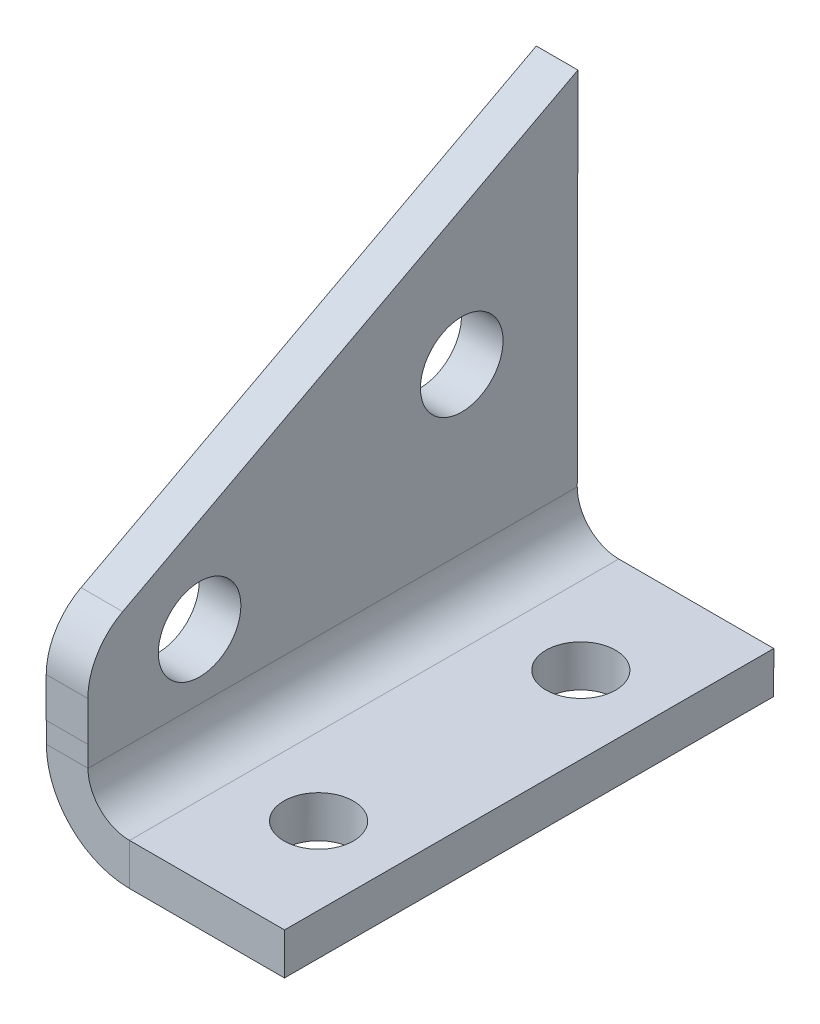
SolidWorks part; units mm, degrees
note: The reader was unsure of these and kept them because the rebuilt part matched: flange length of "Edge-Flange1".
ref_plane "Front Plane" through (0, 0, 0) normal (0, 0, 1) x (1, 0, 0)
ref_plane "Top Plane" through (0, 0, 0) normal (0, 1, 0) x (1, 0, 0)
ref_plane "Right Plane" through (0, 0, 0) normal (1, 0, 0) x (0, 0, -1)
sketch "Sketch2" plane through (0, 0, 0) normal (1, 0, 0) x (0, 0, -1)
  line L0 (83.1061, 32.1051) -> (83.1692, 65.9702)
  line L1 (83.1692, 65.9702) -> (48.4379, 47.5536)
  line L2 (45.7802, 43.1362) -> (45.7802, 32.1746)
  line B0 (99.7947, 74.138) -> (132.5557, 74.2809)
  line B1 (137.5775, 69.3044) -> (137.7293, 36.9329)
  line B2 (84.2276, -6.2892) -> (84.2276, 32.103)
  line B3 (84.2276, 32.103) -> (45.7802, 32.1746)
  line B4 (48.4379, 47.5536) -> (97.4741, 73.5555)
  line B5 (84.2276, -6.2892) -> (105.2373, -6.2892)
  arc B6 (137.5775, 69.3044) -> (132.5557, 74.2809) centre (132.5775, 69.2809) ccw
  arc B7 (99.7947, 74.138) -> (97.4741, 73.5555) centre (99.8165, 69.1381) ccw
  arc B8 (45.7802, 43.1362) -> (48.4379, 47.5536) centre (50.7802, 43.1362) cw
  circle B9 centre (101.1736, 39.1798) radius 1.5
  ellipse B10 centre (132.1723, 39.3181) end of major axis (131.4323, 40.6229) minor radius 1.5
  spline B11 degree 3 poles (111.6938, 43.5404) (116.3311, 42.6396) (120.9601, 43.582) (124.8762, 46.224) (127.4831, 50.1636) (128.3839, 54.8009) (127.4416, 59.43) (124.7995, 63.346) (120.8599, 65.9529) (116.2226, 66.8538) (111.5936, 65.9114) (107.6775, 63.2693) (105.0706, 59.3298) (104.1698, 54.6924) (105.1121, 50.0634) (107.7542, 46.1473) (111.6938, 43.5404) (116.3311, 42.6396) (120.9601, 43.582) knots -1.178097 -0.785398 -0.392699 0 0.392699 0.785398 1.178097 1.570796 1.963495 2.356194 2.748894 3.141593 3.534292 3.926991 4.31969 4.712389 5.105088 5.497787 5.890486 6.283185 6.675884 7.068583 7.461283 only from (116.3297, 42.9468) to (116.3297, 42.9468)
sketch_block_instance "motormount-1"
sketch_block "Block1" parameters "D1"=5
sketch "Sketch3" plane through (0, 0, 0) normal (1, 0, 0) x (0, 0, -1)
  line L0 (84.2276, 32.103) -> (45.7802, 32.1746) construction
  line L1 (45.7802, 43.1362) -> (45.7802, 32.1746) construction
  line L2 (83.1692, 65.9702) -> (48.4379, 47.5536) construction
  line L3 (83.1061, 32.1051) -> (83.1692, 65.9702) construction
  line L4 (83.1061, 32.1051) -> (45.7802, 32.1746)
  line L5 (45.7802, 43.1362) -> (45.7802, 32.1746)
  line L6 (83.1692, 65.9702) -> (48.4379, 47.5536)
  line L7 (83.1061, 32.1051) -> (83.1692, 65.9702)
  arc A0 (48.4379, 47.5536) -> (45.7802, 43.1362) centre (50.7802, 43.1362) ccw construction
  arc A1 (48.4379, 47.5536) -> (45.7802, 43.1362) centre (50.7802, 43.1362) ccw
base flange "Base-Flange1" sketch "Sketch3" thickness 3.175 reverse thickness direction no parameters "D1"=3.175
edge flange "Edge-Flange1" sketch "Sketch13" flange angle 90 flange length 15 flange position material inside bend radius 3.175 thickness 3.175 relief rectangular parameters "D6"=10
sketch "Sketch13" plane through (0, 32.2598, -0.0601) normal (0, 1, -0.0019) x (0, 0.0019, 1)
  line L2 (-83.0462, 0) -> (-83.0462, 15)
  line L3 (-83.0462, 15) -> (-45.7202, 15)
  line L4 (-45.7202, 15) -> (-45.7202, 0)
  line L5 (-45.7202, 0) -> (-83.0462, 0) construction
  line L6 (-45.7202, 0) -> (-83.0462, 0)
bend "EdgeBend1" bend radius 3.175 bend angle 90 parameters "D5"=1
sketch "Sketch15" plane through (0, 35.4348, -0.066) normal (0, 1, -0.0019) x (1, 0, 0)
  line L0 (9.0875, 83.0462) -> (9.0875, 45.7334) construction
  line L1 (15, 83.0462) -> (3.175, 83.0462) construction
  line L2 (-19.341, 123.6071) -> (-19.3381, 109.6071)
  line L3 (-8.3381, 109.6093) -> (-8.341, 123.6093)
  line L4 (-19.3418, 127.5571) -> (-19.3373, 105.6571)
  line L5 (-10.123, 105.659) -> (-10.1275, 127.559)
  line L6 (-8.8373, 105.6592) -> (-8.8418, 127.5592)
  line L7 (-1.8383, 110.6107) -> (-1.8408, 122.6107)
  line L8 (-0.0111, 99.672) -> (-0.0106, 97.3526)
  line L9 (3.1644, 97.3532) -> (3.1639, 99.6727)
  line L10 (3.1641, 98.5178) -> (3.1567, 134.5174)
  line L11 (-0.0178, 132.4327) -> (-0.0111, 99.672)
  line L12 (-0.0178, 132.4327) -> (3.1572, 132.4334)
  line L13 (-0.0189, 137.4637) -> (-0.0178, 132.4327)
  line L14 (-0.0189, 137.4637) -> (3.1561, 137.4644)
  line L15 (13.1561, 137.5329) -> (3.1561, 137.5309)
  line L16 (43.1561, 137.5391) -> (43.1567, 134.5257)
  line L17 (43.1561, 137.5391) -> (33.1561, 137.537)
  line L18 (13.1561, 137.5463) -> (33.1561, 137.5505)
  line L19 (43.1567, 134.5257) -> (43.1641, 98.526)
  line L20 (43.1648, 95.5395) -> (33.1648, 95.5374)
  line L21 (13.1648, 95.5468) -> (33.1648, 95.5509)
  line L22 (13.1648, 95.5333) -> (3.1648, 95.5313)
  line L23 (-0.0111, 99.672) -> (3.1639, 99.6727)
  line L24 (-0.0106, 97.3526) -> (3.1644, 97.3532)
  line L25 (-377.5488, 45.6583) -> (22.4512, 45.736)
  line L26 (-0.0005, 48.3648) -> (0, 45.7154)
  line L27 (3.175, 45.7161) -> (3.1745, 48.3655)
  line L28 (3.1644, 97.3532) -> (3.1745, 48.3655)
  line L29 (-0.0106, 97.3526) -> (-0.0005, 48.3648)
  line L30 (-0.0005, 48.3648) -> (3.1745, 48.3655)
  line L31 (-377.5564, 82.6583) -> (22.4436, 82.7405)
  line L32 (-377.5547, 74.1583) -> (22.4453, 74.2405)
  line L33 (-377.5505, 54.1583) -> (22.4495, 54.2405)
  circle A0 centre (9.0875, 74.2378) radius 2.65
  circle A1 centre (9.0875, 54.2334) radius 2.65
  dimension "D1" = 5.3
  dimension "D2" = 5.3
extrude "Cut-Extrude2" cut sketch "Sketch15" against normal blind 10 contours A0 | A1 normal cut yes
sketch "Sketch19" plane through (-3.175, 0, 0) normal (-1, 0, 0) x (0, 0, 1)
  line L0 (-83.1061, 43.4551) -> (-120.4526, 43.4551) construction
  line L2 (-54.2242, 35.3339) -> (-54.3064, 35.3337) construction
  line L3 (-80.9501, 50.9551) -> (-127.1951, 50.9551) construction
  line L4 (-54.2242, 35.3339) -> (-54.3064, 35.3337)
  line L5 (-54.3064, 35.3337) -> (-54.3064, 53.5849) construction
  line L6 (-74.2242, 35.2966) -> (-74.3064, 35.2965) construction
  line L7 (-74.2242, 35.2966) -> (-74.3064, 35.2965)
  line L8 (-74.3064, 35.2965) -> (-74.3064, 62.4144) construction
  circle A0 centre (-54.3064, 43.4551) radius 3.15
  circle A1 centre (-74.3064, 50.9551) radius 3.15
  dimension "D2" = 6.3
  dimension "D3" = 6.3
  dimension "D1" = 5
  dimension "D4" = 12.5
extrude "Cut-Extrude4" cut sketch "Sketch19" against normal blind 10 contours A1 | A0 normal cut yes
extrude "Cut-Extrude5" [suppressed] cut sketch "Sketch20" against normal blind 10
sketch "Sketch20" plane through (-6.35, -854.8424, -1399.5803) normal (-1, 0, 0) x (0, -0.0044, 1)
  circle A4 centre (1283.9738, 884.2446) radius 3.15
  circle A5 centre (1298.94, 864.2446) radius 3.15
  circle A6 centre (1341.5612, 904.196) radius 3.15
  circle A7 centre (1321.5612, 911.696) radius 3.15
sketch "Bend-Lines1" [suppressed] plane through (0, 0, 0) normal (0, 1, 0) x (1, 0, 0)
sketch "Bounding-Box1" [suppressed] plane through (0, 0, 0) normal (0, 1, 0) x (1, 0, 0)
sheet metal parameters "Sheet-Metal1" thickness 3.175 parameters "D1"=3.175
flat pattern "Flat-Pattern1" [suppressed]
sketch "Bend-Lines2" plane through (0, 0, 0) normal (0, 1, 0) x (1, 0, 0)
sketch3d "Bounding-Box2" [suppressed]
  line L0 (4.9369, 22.9035, 0) -> (-32.389, 22.834, 0) construction
  line L1 (5, -10.9616, 0) -> (-32.3259, -11.0311, 0) construction
  line L2 (4.9369, 22.9035, 0) -> (5, -10.9616, 0) construction
  line L3 (-32.389, 22.834, 0) -> (-32.3259, -11.0311, 0) construction
sheet metal parameters "Sheet-Metal3" thickness 3.175 parameters "D1"=3.175
flat pattern "Flat-Pattern1" [suppressed]
sketch "Bend-Lines2" plane through (0, 0, 0) normal (1, 0, 0) x (0, 0, -1)
  line L0 (45.7854, 34.9338) -> (83.1113, 34.8642) construction
  line L1 (45.7854, 34.9338) -> (83.1113, 34.8642) construction
sketch3d "Bounding-Box2" [suppressed]
  line L0 (32.3024, -23.6878, 0) -> (32.389, 22.834, 0) construction
  line L1 (-5.0236, -23.6182, 0) -> (-4.9369, 22.9035, 0) construction
  line L2 (32.3024, -23.6878, 0) -> (-5.0236, -23.6182, 0) construction
  line L3 (32.389, 22.834, 0) -> (-4.9369, 22.9035, 0) construction
bend of the flat pattern "Flatten-<EdgeBend1>1"
sketch "Sketch14-1" [suppressed] plane through (-3.175, 37.7781, -0.0704) normal (-1, 0, 0) x (0, 1, -0.0019)
  line L5 (-12.2625, 83.0462) -> (-12.2625, 45.7202) construction
  line L6 (-18.175, 83.0462) -> (28.3468, 83.0462) construction
  circle A0 centre (-12.2625, 73.0462) radius 3.15
  circle A1 centre (-12.2625, 53.0462) radius 3.15
  dimension "D1" = 6.3
  dimension "D2" = 6.3
  dimension "D3" = 10
  dimension "D4" = 20
sketch "Sketch15-2" [suppressed] plane through (-3.175, 37.7781, -0.0704) normal (-1, 0, 0) x (0, 1, -0.0019)
sheet metal parameters "Sheet-Metal5" thickness 3.175 parameters "D1"=3.175
flat pattern "Flat-Pattern1" [suppressed]
sketch "Bend-Lines2" plane through (0, 0, 0) normal (1, 0, 0) x (0, 0, -1)
  line L0 (45.7854, 34.9338) -> (83.1113, 34.8642) construction
  line L1 (45.7854, 34.9338) -> (83.1113, 34.8642) construction
sketch3d "Bounding-Box2" [suppressed]
  line L0 (32.3024, -23.6878, 0) -> (32.389, 22.834, 0) construction
  line L1 (-5.0236, -23.6182, 0) -> (-4.9369, 22.9035, 0) construction
  line L2 (32.3024, -23.6878, 0) -> (-5.0236, -23.6182, 0) construction
  line L3 (32.389, 22.834, 0) -> (-4.9369, 22.9035, 0) construction
bend of the flat pattern "Flatten-<EdgeBend1>1"
sketch "Sketch15-2" [suppressed] plane through (-3.175, 37.7781, -0.0704) normal (-1, 0, 0) x (0, 1, -0.0019)
  line L0 (-12.2625, 83.0462) -> (-12.2625, 45.7334) construction
  line L2 (-19.341, 123.6071) -> (-19.3381, 109.6071)
  line L3 (-8.3381, 109.6093) -> (-8.341, 123.6093)
  line L4 (-19.3418, 127.5571) -> (-19.3373, 105.6571)
  line L5 (-10.123, 105.659) -> (-10.1275, 127.559)
  line L6 (-8.8373, 105.6592) -> (-8.8418, 127.5592)
  line L7 (-1.8383, 110.6107) -> (-1.8408, 122.6107)
  line L8 (-0.0111, 99.672) -> (-0.0106, 97.3526)
  line L9 (3.1644, 97.3532) -> (3.1639, 99.6727)
  line L10 (3.1641, 98.5178) -> (3.1567, 134.5174)
  line L11 (-0.0178, 132.4327) -> (-0.0111, 99.672)
  line L12 (-0.0178, 132.4327) -> (3.1572, 132.4334)
  line L13 (-0.0189, 137.4637) -> (-0.0178, 132.4327)
  line L14 (-0.0189, 137.4637) -> (3.1561, 137.4644)
  line L15 (13.1561, 137.5329) -> (3.1561, 137.5309)
  line L16 (43.1561, 137.5391) -> (43.1567, 134.5257)
  line L17 (43.1561, 137.5391) -> (33.1561, 137.537)
  line L18 (13.1561, 137.5463) -> (33.1561, 137.5505)
  line L19 (43.1567, 134.5257) -> (43.1641, 98.526)
  line L20 (43.1648, 95.5395) -> (33.1648, 95.5374)
  line L21 (13.1648, 95.5468) -> (33.1648, 95.5509)
  line L22 (13.1648, 95.5333) -> (3.1648, 95.5313)
  line L23 (-0.0111, 99.672) -> (3.1639, 99.6727)
  line L24 (-0.0106, 97.3526) -> (3.1644, 97.3532)
  line L25 (-377.5488, 45.6583) -> (22.4512, 45.7405)
  line L26 (-0.0005, 48.3648) -> (0, 45.7154)
  line L27 (3.175, 45.7161) -> (3.1745, 48.3655)
  line L28 (3.1644, 97.3532) -> (3.1745, 48.3655)
  line L29 (-0.0106, 97.3526) -> (-0.0005, 48.3648)
  line L30 (-0.0005, 48.3648) -> (3.1745, 48.3655)
  line L31 (-377.5564, 82.6583) -> (22.4436, 82.7405)
  line L32 (-377.5547, 74.1583) -> (22.4453, 74.2405)
  line L33 (-377.5505, 54.1583) -> (22.4495, 54.2405)
  circle A0 centre (-12.2625, 74.2334) radius 3.15
  circle A1 centre (-12.2625, 54.2334) radius 3.15
  dimension "D1" = 6.3
sheet metal parameters "Sheet-Metal7" thickness 3.175 parameters "D1"=3.175
flat pattern "Flat-Pattern1" [suppressed]
sketch "Bend-Lines2" plane through (0, 0, 0) normal (1, 0, 0) x (0, 0, -1)
  line L0 (45.7854, 34.9338) -> (83.1113, 34.8642) construction
  line L1 (45.7854, 34.9338) -> (83.1113, 34.8642) construction
sketch3d "Bounding-Box2" [suppressed]
  line L0 (32.3024, -23.6878, 0) -> (32.389, 22.834, 0) construction
  line L1 (-5.0236, -23.6182, 0) -> (-4.9369, 22.9035, 0) construction
  line L2 (32.3024, -23.6878, 0) -> (-5.0236, -23.6182, 0) construction
  line L3 (32.389, 22.834, 0) -> (-4.9369, 22.9035, 0) construction
bend of the flat pattern "Flatten-<EdgeBend1>1"
sketch "Sketch15-2" [suppressed] plane through (0, 34.6031, -0.0645) normal (1, 0, 0) x (0, -1, 0.0019)
  line L0 (9.0875, 83.0462) -> (9.0875, 45.7334) construction
  line L2 (-19.341, 123.6071) -> (-19.3381, 109.6071)
  line L3 (-8.3381, 109.6093) -> (-8.341, 123.6093)
  line L4 (-19.3418, 127.5571) -> (-19.3373, 105.6571)
  line L5 (-10.123, 105.659) -> (-10.1275, 127.559)
  line L6 (-8.8373, 105.6592) -> (-8.8418, 127.5592)
  line L7 (-1.8383, 110.6107) -> (-1.8408, 122.6107)
  line L8 (-0.0111, 99.672) -> (-0.0106, 97.3526)
  line L9 (3.1644, 97.3532) -> (3.1639, 99.6727)
  line L10 (3.1641, 98.5178) -> (3.1567, 134.5174)
  line L11 (-0.0178, 132.4327) -> (-0.0111, 99.672)
  line L12 (-0.0178, 132.4327) -> (3.1572, 132.4334)
  line L13 (-0.0189, 137.4637) -> (-0.0178, 132.4327)
  line L14 (-0.0189, 137.4637) -> (3.1561, 137.4644)
  line L15 (13.1561, 137.5329) -> (3.1561, 137.5309)
  line L16 (43.1561, 137.5391) -> (43.1567, 134.5257)
  line L17 (43.1561, 137.5391) -> (33.1561, 137.537)
  line L18 (13.1561, 137.5463) -> (33.1561, 137.5505)
  line L19 (43.1567, 134.5257) -> (43.1641, 98.526)
  line L20 (43.1648, 95.5395) -> (33.1648, 95.5374)
  line L21 (13.1648, 95.5468) -> (33.1648, 95.5509)
  line L22 (13.1648, 95.5333) -> (3.1648, 95.5313)
  line L23 (-0.0111, 99.672) -> (3.1639, 99.6727)
  line L24 (-0.0106, 97.3526) -> (3.1644, 97.3532)
  line L25 (-377.5488, 45.6583) -> (22.4512, 45.736)
  line L26 (-0.0005, 48.3648) -> (0, 45.7154)
  line L27 (3.175, 45.7161) -> (3.1745, 48.3655)
  line L28 (3.1644, 97.3532) -> (3.1745, 48.3655)
  line L29 (-0.0106, 97.3526) -> (-0.0005, 48.3648)
  line L30 (-0.0005, 48.3648) -> (3.1745, 48.3655)
  line L31 (-377.5564, 82.6583) -> (22.4436, 82.7405)
  line L32 (-377.5547, 74.1583) -> (22.4453, 74.2405)
  line L33 (-377.5505, 54.1583) -> (22.4495, 54.2405)
  circle A0 centre (9.0875, 74.2378) radius 2.65
  circle A1 centre (9.0875, 54.2334) radius 2.65
  dimension "D1" = 5.3
  dimension "D2" = 5.3
sheet metal parameters "Sheet-Metal8" thickness 3.175 parameters "D1"=3.175
flat pattern "Flat-Pattern1" [suppressed]
sketch "Bend-Lines2" plane through (0, 0, 0) normal (1, 0, 0) x (0, 0, -1)
  line L0 (45.7854, 34.9338) -> (83.1113, 34.8642) construction
  line L1 (45.7854, 34.9338) -> (83.1113, 34.8642) construction
sketch3d "Bounding-Box2" [suppressed]
  line L0 (32.3024, -23.6878, 0) -> (32.389, 22.834, 0) construction
  line L1 (-5.0236, -23.6182, 0) -> (-4.9369, 22.9035, 0) construction
  line L2 (32.3024, -23.6878, 0) -> (-5.0236, -23.6182, 0) construction
  line L3 (32.389, 22.834, 0) -> (-4.9369, 22.9035, 0) construction
bend of the flat pattern "Flatten-<EdgeBend1>1"
sketch "Sketch15-2" plane through (0, 34.6031, -0.0645) normal (1, 0, 0) x (0, -1, 0.0019)
  line L0 (9.0875, 83.0462) -> (9.0875, 45.7334) construction
  line L2 (-19.341, 123.6071) -> (-19.3381, 109.6071)
  line L3 (-8.3381, 109.6093) -> (-8.341, 123.6093)
  line L4 (-19.3418, 127.5571) -> (-19.3373, 105.6571)
  line L5 (-10.123, 105.659) -> (-10.1275, 127.559)
  line L6 (-8.8373, 105.6592) -> (-8.8418, 127.5592)
  line L7 (-1.8383, 110.6107) -> (-1.8408, 122.6107)
  line L8 (-0.0111, 99.672) -> (-0.0106, 97.3526)
  line L9 (3.1644, 97.3532) -> (3.1639, 99.6727)
  line L10 (3.1641, 98.5178) -> (3.1567, 134.5174)
  line L11 (-0.0178, 132.4327) -> (-0.0111, 99.672)
  line L12 (-0.0178, 132.4327) -> (3.1572, 132.4334)
  line L13 (-0.0189, 137.4637) -> (-0.0178, 132.4327)
  line L14 (-0.0189, 137.4637) -> (3.1561, 137.4644)
  line L15 (13.1561, 137.5329) -> (3.1561, 137.5309)
  line L16 (43.1561, 137.5391) -> (43.1567, 134.5257)
  line L17 (43.1561, 137.5391) -> (33.1561, 137.537)
  line L18 (13.1561, 137.5463) -> (33.1561, 137.5505)
  line L19 (43.1567, 134.5257) -> (43.1641, 98.526)
  line L20 (43.1648, 95.5395) -> (33.1648, 95.5374)
  line L21 (13.1648, 95.5468) -> (33.1648, 95.5509)
  line L22 (13.1648, 95.5333) -> (3.1648, 95.5313)
  line L23 (-0.0111, 99.672) -> (3.1639, 99.6727)
  line L24 (-0.0106, 97.3526) -> (3.1644, 97.3532)
  line L25 (-377.5488, 45.6583) -> (22.4512, 45.736)
  line L26 (-0.0005, 48.3648) -> (0, 45.7154)
  line L27 (3.175, 45.7161) -> (3.1745, 48.3655)
  line L28 (3.1644, 97.3532) -> (3.1745, 48.3655)
  line L29 (-0.0106, 97.3526) -> (-0.0005, 48.3648)
  line L30 (-0.0005, 48.3648) -> (3.1745, 48.3655)
  line L31 (-377.5564, 82.6583) -> (22.4436, 82.7405)
  line L32 (-377.5547, 74.1583) -> (22.4453, 74.2405)
  line L33 (-377.5505, 54.1583) -> (22.4495, 54.2405)
  circle A0 centre (9.0875, 74.2378) radius 3.15
  circle A1 centre (9.0875, 54.2334) radius 3.15
  dimension "D1" = 6.3
